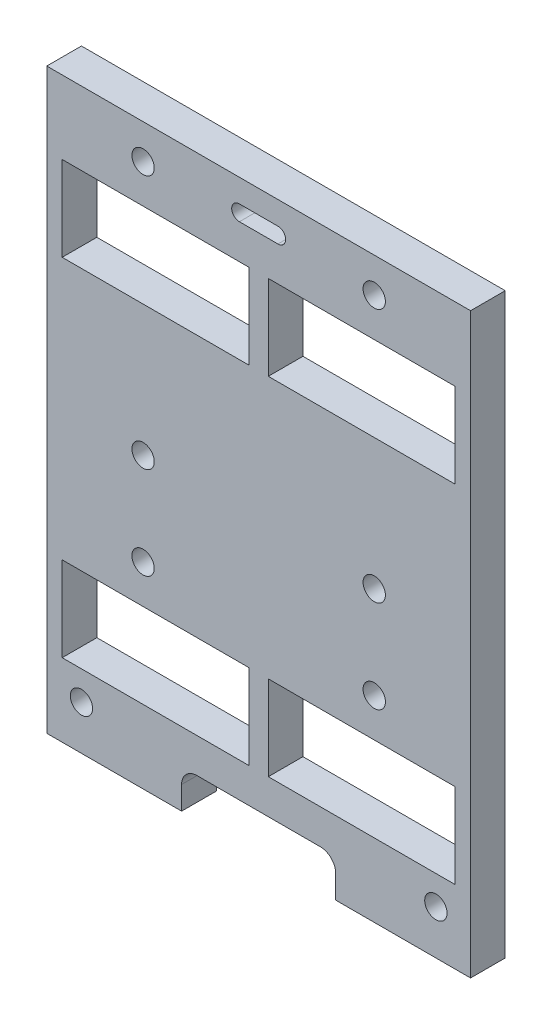
SolidWorks part; units mm, degrees
ref_plane "Front Plane" through (0, 0, 0) normal (0, 0, 1) x (1, 0, 0)
ref_plane "Top Plane" through (0, 0, 0) normal (0, 1, 0) x (1, 0, 0)
ref_plane "Right Plane" through (0, 0, 0) normal (1, 0, 0) x (0, 0, -1)
sketch "Sketch1" plane through (0, 0, 0) normal (0, 0, 1) x (1, 0, 0)
  line L0 (0, -37.5) -> (0, 37.5) construction
  line L1 (-27.5, -37.5) -> (27.5, -37.5)
  line L2 (-27.5, -37.5) -> (-27.5, 37.5)
  line L3 (-27.5, 37.5) -> (27.5, 37.5)
  line L4 (27.5, -37.5) -> (27.5, 37.5)
  line L5 (-27.5, -37.5) -> (27.5, 37.5) construction
  line L6 (-27.5, 37.5) -> (27.5, -37.5) construction
  line L7 (-27.5, 0) -> (27.5, 0) construction
  line L8 (-27.5, 22.5) -> (27.5, 22.5) construction
  line L9 (25.5, 17) -> (1.25, 28) construction
  line L10 (-25.5, 28) -> (-1.25, 28)
  line L11 (-25.5, 28) -> (-25.5, 17)
  line L12 (-25.5, 17) -> (-1.25, 17)
  line L13 (-1.25, 28) -> (-1.25, 17)
  line L14 (-25.5, 28) -> (-1.25, 17) construction
  line L15 (-25.5, 17) -> (-1.25, 28) construction
  line L16 (25.5, 28) -> (1.25, 17) construction
  line L17 (1.25, 28) -> (1.25, 17)
  line L18 (25.5, 17) -> (1.25, 17)
  line L19 (25.5, 28) -> (25.5, 17)
  line L20 (25.5, 28) -> (1.25, 28)
  line L21 (25.5, -28) -> (1.25, -17) construction
  line L22 (-25.5, -17) -> (-1.25, -28) construction
  line L23 (-25.5, -28) -> (-1.25, -17) construction
  line L24 (25.5, -17) -> (1.25, -28) construction
  line L25 (25.5, -28) -> (1.25, -28)
  line L26 (25.5, -28) -> (25.5, -17)
  line L27 (25.5, -17) -> (1.25, -17)
  line L28 (1.25, -28) -> (1.25, -17)
  line L29 (-1.25, -28) -> (-1.25, -17)
  line L30 (-25.5, -17) -> (-1.25, -17)
  line L31 (-25.5, -28) -> (-25.5, -17)
  line L32 (-25.5, -28) -> (-1.25, -28)
  point P0 (0, 0)
  point P12 (-13.375, 22.5)
  point P21 (13.375, 22.5)
  point P30 (13.375, -22.5)
  point P31 (-13.375, -22.5)
  dimension "D1" = 55
  dimension "D2" = 75
  dimension "D3" = 22.5
  dimension "D4" = 24.25
  dimension "D5" = 11
  dimension "D6" = 1.25
extrude "Boss-Extrude1" add sketch "Sketch1" along normal blind 4.5
sketch "Sketch2" plane through (0, 0, 4.5) normal (0, 0, 1) x (1, 0, 0)
  line L0 (0, -37.5) -> (0, 37.5) construction
  line L1 (-27.5, -37.5) -> (27.5, -37.5) construction
  line L2 (27.5, 37.5) -> (-27.5, 37.5) construction
  line L3 (-27.5, 0) -> (27.5, 0) construction
  line L4 (-27.5, 37.5) -> (-27.5, -37.5) construction
  line L5 (27.5, -37.5) -> (27.5, 37.5) construction
  line L6 (-15, 0) -> (15, 0) construction
  circle A0 centre (-15, 33) radius 1.45
  circle A1 centre (15, 33) radius 1.45
  circle A2 centre (15, 0) radius 1.45
  circle A3 centre (-15, 0) radius 1.45
  dimension "D1" = 2.9
  dimension "D7" = 2.9
  dimension "D8" = 2.9
  dimension "D2" = 15
  dimension "D3" = 33
  dimension "D4" = 30
  dimension "D5" = 15
  dimension "D6" = 0
extrude "screwHoles" cut sketch "Sketch2" against normal through all
sketch "Sketch3" plane through (0, 0, 4.5) normal (0, 0, 1) x (1, 0, 0)
  line L0 (-27.5, 9) -> (26.0486, 9) construction
  line L1 (-27.5, 37.5) -> (-27.5, -37.5) construction
  line L3 (0, 37.5) -> (0, -37.5) construction
  line L4 (27.5, 37.5) -> (-27.5, 37.5) construction
  line L5 (-27.5, -37.5) -> (27.5, -37.5) construction
  line L6 (18.95, 6.8) -> (9.05, 11.2) construction
  line L7 (-18.95, 11.2) -> (-9.05, 11.2)
  line L8 (-18.95, 11.2) -> (-18.95, 6.8)
  line L9 (-18.95, 6.8) -> (-9.05, 6.8)
  line L10 (-9.05, 11.2) -> (-9.05, 6.8)
  line L11 (-18.95, 11.2) -> (-9.05, 6.8) construction
  line L12 (-18.95, 6.8) -> (-9.05, 11.2) construction
  line L13 (18.95, 11.2) -> (9.05, 6.8) construction
  line L14 (9.05, 11.2) -> (9.05, 6.8)
  line L15 (18.95, 6.8) -> (9.05, 6.8)
  line L16 (18.95, 11.2) -> (18.95, 6.8)
  line L17 (18.95, 11.2) -> (9.05, 11.2)
  line L18 (-27.5, 37.5) -> (-27.5, -37.5) construction
  point P2 (-27.5, 0)
  point P12 (-14, 9)
  point P21 (14, 9)
  dimension "D1" = 9.9
  dimension "D3" = 14
  dimension "D4" = 9
extrude "BeltClamp" [suppressed] cut sketch "Sketch3" against normal through all
sketch "Sketch4" plane through (0, 0, 4.5) normal (0, 0, 1) x (1, 0, 0)
  line L0 (-27.5, 0) -> (27.5, 0) construction
  line L1 (-27.5, 37.5) -> (-27.5, -37.5) construction
  line L2 (27.5, -37.5) -> (27.5, 37.5) construction
  line L4 (-4.85, 2.175) -> (4.85, 2.175)
  line L5 (-4.85, 2.175) -> (-4.85, -2.175)
  line L6 (-4.85, -2.175) -> (4.85, -2.175)
  line L7 (4.85, 2.175) -> (4.85, -2.175)
  line L8 (-4.85, 2.175) -> (4.85, -2.175) construction
  line L9 (-4.85, -2.175) -> (4.85, 2.175) construction
  circle A0 centre (-15, 0) radius 1.45 construction
  point P6 (0, 0)
  dimension "D2" = 4.35
  dimension "D3" = 0
extrude "mountingPlateTab" [suppressed] cut sketch "Sketch4" against normal through all
sketch "Sketch5" plane through (0, 0, 4.5) normal (0, 0, 1) x (1, 0, 0)
  line L0 (-27.5, -9.75) -> (27.5, -9.75) construction
  line L1 (-27.5, 37.5) -> (-27.5, -37.5) construction
  line L2 (27.5, -37.5) -> (27.5, 37.5) construction
  line L4 (0, -37.5) -> (0, 37.5) construction
  line L5 (-27.5, -37.5) -> (27.5, -37.5) construction
  line L6 (27.5, 37.5) -> (-27.5, 37.5) construction
  line L7 (-20.825, -14.6) -> (-25.175, -4.9) construction
  line L8 (20.825, -4.9) -> (25.175, -4.9)
  line L9 (20.825, -4.9) -> (20.825, -14.6)
  line L10 (20.825, -14.6) -> (25.175, -14.6)
  line L11 (25.175, -4.9) -> (25.175, -14.6)
  line L12 (20.825, -4.9) -> (25.175, -14.6) construction
  line L13 (20.825, -14.6) -> (25.175, -4.9) construction
  line L14 (-20.825, -4.9) -> (-25.175, -14.6) construction
  line L15 (-25.175, -4.9) -> (-25.175, -14.6)
  line L16 (-20.825, -14.6) -> (-25.175, -14.6)
  line L17 (-20.825, -4.9) -> (-20.825, -14.6)
  line L18 (-20.825, -4.9) -> (-25.175, -4.9)
  line L19 (23, -9.75) -> (23, -37.5) construction
  line L20 (-23, -9.75) -> (-23, -37.5) construction
  circle A0 centre (23, -31.75) radius 1.45
  circle A1 centre (-23, -31.75) radius 1.45
  point P15 (23, -9.75)
  point P24 (-23, -9.75)
  dimension "D5" = 2.9
  dimension "D2" = 9.7
  dimension "D3" = 4.35
  dimension "D4" = 23
  dimension "D6" = 22
  dimension "D1" = 9.75
extrude "BraceTabs" cut sketch "Sketch5" against normal through all
sketch "Sketch6" [suppressed] plane through (0, 0, 4.5) normal (0, 0, 1) x (1, 0, 0)
  line L0 (-25.175, -9.75) -> (25.175, -9.75) construction
  line L1 (-25.175, -4.9) -> (-25.175, -14.6) construction
  line L2 (25.175, -14.6) -> (25.175, -4.9) construction
  line L3 (0, -2.175) -> (0, -37.5) construction
  line L4 (-4.85, -2.175) -> (4.85, -2.175) construction
  line L5 (-27.5, -37.5) -> (27.5, -37.5) construction
  line L6 (23, -14.6) -> (23, -4.9) construction
  line L7 (20.825, -14.6) -> (25.175, -14.6) construction
  line L8 (25.175, -4.9) -> (20.825, -4.9) construction
  line L9 (20.825, -4.9) -> (20.825, -14.6) construction
  line L10 (19.825, -15.6) -> (26.175, -15.6)
  line L11 (19.825, -15.6) -> (19.825, -3.9)
  line L12 (19.825, -3.9) -> (26.175, -3.9)
  line L13 (26.175, -15.6) -> (26.175, -3.9)
  line L14 (19.825, -15.6) -> (26.175, -3.9) construction
  line L15 (19.825, -3.9) -> (26.175, -15.6) construction
  line L16 (-19.825, -3.9) -> (-26.175, -15.6) construction
  line L17 (-19.825, -15.6) -> (-26.175, -3.9) construction
  line L18 (-23, -14.6) -> (-23, -4.9) construction
  line L19 (-26.175, -15.6) -> (-26.175, -3.9)
  line L20 (-19.825, -3.9) -> (-26.175, -3.9)
  line L21 (-19.825, -15.6) -> (-19.825, -3.9)
  line L22 (-19.825, -15.6) -> (-26.175, -15.6)
  circle A0 centre (23, -9.75) radius 1.45
  circle A1 centre (-23, -9.75) radius 1.45
  point P18 (23, -9.75)
  dimension "D3" = 2.9
  dimension "D1" = 1
  dimension "D2" = 1
extrude "FrontToRear1" [suppressed] add sketch "Sketch6" against normal up to surface (4.5 mm away) up to face at (-24.45, -31.75, 0)
sketch "Sketch7" [suppressed] plane through (0, 0, 4.5) normal (0, 0, 1) x (1, 0, 0)
  line L0 (4.85, 2.175) -> (-4.85, 2.175) construction
  line L1 (-20, -3.175) -> (20, -3.175)
  line L2 (-20, -3.175) -> (-20, 3.175)
  line L3 (-20, 3.175) -> (20, 3.175)
  line L4 (20, -3.175) -> (20, 3.175)
  line L5 (-20, -3.175) -> (20, 3.175) construction
  line L6 (-20, 3.175) -> (20, -3.175) construction
  circle A0 centre (15, 0) radius 1.45 construction
  point P0 (0, 0)
  dimension "D1" = 1
  dimension "D2" = 5
extrude "FrontToRear2" [suppressed] add sketch "Sketch7" against normal through all
sketch "Sketch8" plane through (0, 0, 4.5) normal (0, 0, 1) x (1, 0, 0)
  line L0 (-27.5, -12) -> (27.5, -12) construction
  line L1 (-27.5, 37.5) -> (-27.5, -37.5) construction
  line L2 (27.5, -37.5) -> (27.5, 37.5) construction
  line L3 (0, -37.5) -> (0, 0) construction
  line L4 (-27.5, -37.5) -> (27.5, -37.5) construction
  circle A0 centre (-15, -12) radius 1.45
  circle A1 centre (15, -12) radius 1.45
  dimension "D2" = 2.9
  dimension "D1" = 12
  dimension "D3" = 15
extrude "ExpansionScrewholes" cut sketch "Sketch8" against normal through all
sketch "Sketch12" plane through (0, 0, 4.5) normal (0, 0, 1) x (1, 0, 0)
  line L0 (0, 37.5) -> (0, 0) construction
  line L1 (27.5, 37.5) -> (-27.5, 37.5) construction
  line L2 (-2.5, 33.5) -> (2.5, 33.5) construction
  line L3 (-2.5, 34.5) -> (2.5, 34.5)
  line L4 (-2.5, 32.5) -> (2.5, 32.5)
  arc A0 (-2.5, 34.5) -> (-2.5, 32.5) centre (-2.5, 33.5) ccw
  arc A1 (2.5, 32.5) -> (2.5, 34.5) centre (2.5, 33.5) ccw
  point P7 (0, 33.5)
  dimension "D1" = 3
  dimension "D2" = 2
  dimension "D3" = 5
extrude "CableTieSlot" cut sketch "Sketch12" against normal through all
sketch "Sketch11" plane through (0, 0, 4.5) normal (0, 0, 1) x (1, 0, 0)
  line L0 (13.5615, -8.6) -> (27.5, -8.6) construction
  line L1 (27.5, -37.5) -> (27.5, 37.5) construction
  line L2 (0, 37.5) -> (0, -37.5) construction
  line L3 (36.5, -14.6) -> (18.5, -14.6)
  line L4 (36.5, -14.6) -> (36.5, -2.6)
  line L5 (36.5, -2.6) -> (18.5, -2.6)
  line L6 (18.5, -14.6) -> (18.5, -2.6)
  line L7 (36.5, -14.6) -> (18.5, -2.6) construction
  line L8 (36.5, -2.6) -> (18.5, -14.6) construction
  line L11 (-36.5, -2.6) -> (-18.5, -14.6) construction
  line L12 (-36.5, -14.6) -> (-18.5, -2.6) construction
  line L13 (-18.5, -14.6) -> (-18.5, -2.6)
  line L14 (-36.5, -2.6) -> (-18.5, -2.6)
  line L15 (-36.5, -14.6) -> (-36.5, -2.6)
  line L16 (-36.5, -14.6) -> (-18.5, -14.6)
  line L17 (36.5, -2.6) -> (18.5, -14.6) construction
  line L18 (20.825, -14.6) -> (25.175, -14.6) construction
  line L19 (27.5, 37.5) -> (-27.5, 37.5) construction
  line L20 (-27.5, -37.5) -> (27.5, -37.5) construction
  dimension "D1" = 9
  dimension "D2" = 12
  dimension "D3" = 0
extrude "Cut-Extrude2" [suppressed] cut sketch "Sketch11" against normal through all
sketch "Sketch10" [suppressed] plane through (0, 0, 4.5) normal (0, 0, 1) x (1, 0, 0)
  line L0 (4.7446, 1) -> (27.5, 1) construction
  line L1 (-4.85, 0) -> (4.85, 0) construction
  line L2 (27.5, -37.5) -> (27.5, 37.5) construction
  line L3 (0, 2.175) -> (0, -2.175) construction
  line L4 (36.5, 4) -> (18.5, 4)
  line L5 (36.5, 4) -> (36.5, -2)
  line L6 (36.5, -2) -> (18.5, -2)
  line L7 (18.5, 4) -> (18.5, -2)
  line L8 (36.5, 4) -> (18.5, -2) construction
  line L9 (36.5, -2) -> (18.5, 4) construction
  line L10 (4.85, 2.175) -> (-4.85, 2.175) construction
  line L11 (-4.85, -2.175) -> (4.85, -2.175) construction
  line L12 (-36.5, -2) -> (-18.5, 4) construction
  line L13 (-36.5, 4) -> (-18.5, -2) construction
  line L14 (-4.7446, 1) -> (-27.5, 1) construction
  line L15 (-18.5, 4) -> (-18.5, -2)
  line L16 (-36.5, -2) -> (-18.5, -2)
  line L17 (-36.5, 4) -> (-36.5, -2)
  line L18 (-36.5, 4) -> (-18.5, 4)
  line L19 (36.5, -2) -> (18.5, 4) construction
  line L20 (-4.85, 2.175) -> (-4.85, -2.175) construction
  line L21 (4.85, -2.175) -> (4.85, 2.175) construction
  dimension "D1" = 6
  dimension "D2" = 9
  dimension "D3" = 1
extrude "CableTieSlots" [suppressed] cut sketch "Sketch10" against normal through all
sketch "Sketch9" plane through (0, 0, 4.5) normal (0, 0, 1) x (1, 0, 0)
  line L0 (-27.5, -37.5) -> (27.5, -37.5) construction
  line L5 (-10, -42.5) -> (10, -42.5)
  line L6 (-10, -42.5) -> (-10, -34.5)
  line L7 (-8, -32.5) -> (8, -32.5)
  line L8 (10, -42.5) -> (10, -34.5)
  line L9 (-10, -42.5) -> (10, -32.5) construction
  line L10 (-10, -32.5) -> (10, -42.5) construction
  arc A0 (8, -32.5) -> (10, -34.5) centre (8, -34.5) cw
  arc A1 (-10, -34.5) -> (-8, -32.5) centre (-8, -34.5) cw
  point P9 (0, -37.5)
  line M42 (-27.5, -37.5) -> (27.5, -37.5)
  dimension "D3" = 2
  dimension "D1" = 20
  dimension "D2" = 5
extrude "RearFanSlot" cut sketch "Sketch9" against normal through all contours A1 L6 L8 A0 L7 M42 | L5 L8 L6 M42
sketch "Sketch13" [suppressed] plane through (0, 0, 4.5) normal (0, 0, 1) x (1, 0, 0)
  line L1 (-7, -2.85) -> (7, -2.85)
  line L2 (-7, -2.85) -> (-7, -11.85)
  line L3 (-7, -11.85) -> (7, -11.85)
  line L4 (7, -2.85) -> (7, -11.85)
  line L5 (-7, -2.85) -> (7, -11.85) construction
  line L6 (-7, -11.85) -> (7, -2.85) construction
  line L9 (0, 37.5) -> (0, -7.35) construction
  line L10 (-18.5, -2.85) -> (-27.5, -2.85) construction
  line L11 (27.5, 37.5) -> (-27.5, 37.5) construction
  line L13 (-27.5, -14.85) -> (-18.5, -14.85) construction
  point P0 (0, -7.35)
  dimension "D1" = 3
  dimension "D2" = 0
  dimension "D3" = 7
extrude "Cut-Extrude3" [suppressed] cut sketch "Sketch13" against normal through all
sketch "Sketch14" plane through (0, 0, 4.5) normal (0, 0, 1) x (1, 0, 0)
  line L0 (25.175, -4.9) -> (20.825, -4.9) construction
  line L1 (25.175, -4.9) -> (20.825, -4.9)
  line L2 (25.175, -4.9) -> (25.175, -14.6)
  line L3 (25.175, -14.6) -> (20.825, -14.6)
  line L4 (20.825, -4.9) -> (20.825, -14.6)
  line L5 (25.175, -14.6) -> (25.175, -4.9) construction
  line L6 (0, 0) -> (0, -6.835) construction
  line L7 (-20.825, -4.9) -> (-20.825, -14.6)
  line L8 (-25.175, -14.6) -> (-20.825, -14.6)
  line L9 (-25.175, -4.9) -> (-25.175, -14.6)
  line L10 (-25.175, -4.9) -> (-20.825, -4.9)
extrude "Boss-Extrude2" add sketch "Sketch14" against normal through all
equation "\"X-ROD-SPACING\"=45"
equation "\"Y-ROD-SPACING\"=75"
equation "\"Z-ROD-SPACING\"=17.5"
equation "\"Y-BED-OFFSET\"=2"
equation "\"Y-BED-ROD-INSET\"=3.5"
equation "\"Y-BED-SCREW-SPACING\"=209"
equation "\"Y-BED-SCREW-CUTOUT-SLOT-HEIGHT\"=2.5"
equation "\"T-SLOT-NUT-FILLET-RADIUS\"=0.5"
equation "\"T-SLOT-SCREW-SHAFT-RADIUS\"=1.55"
equation "\"T-SLOT-SCREW-SHAFT-CUTOUT-LENGTH\"=11"
equation "\"T-SLOT-NUT-DEPTH\"=3.5"
equation "\"T-SLOT-NUT-WIDTH\"=2.85"
equation "\"T-SLOT-NUT-END-DISTANCE\"=8"
equation "\"ACRYLIC-THICKNESS\"=10"
equation "\"ACRYLIC-THICKNESS2\"=4.5"
equation "\"ACRYLIC-TAB-CUTOUT-SIZE\"=\"ACRYLIC-THICKNESS\"+\"ACRYLIC-TAB-TOLERANCE\"*2"
equation "\"ACRYLIC-TAB-WIDTH\"=\"ACRYLIC-THICKNESS\""
equation "\"ACRYLIC-M3-HOLE\"=2.9"
equation "\"SMOOTHROD-CAP-SCREW-DISTANCE\"=20"
equation "\"FRAME-WIDTH-INNER\"=370"
equation "\"NEMA17-HOLE-SPACING\"=31"
equation "\"NEMA17-CENTRAL-CUTOUT\"=22.5"
equation "\"Z-BRACKET-REACH\"=57"
equation "\"Z-ROD-INSET\"=13.5"
equation "\"TOP-BRACKET-SPACING\"=40"
equation "\"SMOOTHROD-X-LENGTH\"=350"
equation "\"SMOOTHROD-Y-LENGTH\"=350"
equation "\"SMOOTHROD-Z-LENGTH\"=350"
equation "\"SMOOTHROD-TIGHTENING-HEADROOM\"=.25"
equation "\"LEADSCREW-Z-LENGTH\"=300"
equation "\"SCREW-LENGTH-FRAME\"=\"ACRYLIC-THICKNESS\" + 10"
equation "\"SCREW-LENGTH-MOTOR\"=\"ACRYLIC-THICKNESS\" + 5"
equation "\"SCREW-HEAD-RADIUS\"=6"
equation "\"PRINTED-X-SMOOTHROD-DIAMETER\"=8.8"
equation "\"PRINTED-X-SMOOTHROD-CUTOUT\"=10"
equation "\"PRINTED-X-BASE-HEIGHT\"=10"
equation "\"PRINTED-LM8UU-CUTOUT-SIZE\"=15.5"
equation "\"PRINTED-LM8UU-CUTOUT-LENGTH\"=24.5"
equation "\"PRINTED-X-IDLER-HEIGHT\"=16"
equation "\"PSU-MOUNTING-WIDTH\"=50"
equation "\"PSU-MOUNTING-HEIGHT\"=150"
equation "\"Y-BELT-TO-ROD-DISTANCE\"=20"
equation "\"SPOOL-HOLDER-ROD-SPACING\"=150"
equation "\"D3@Sketch1\"=\"X-ROD-SPACING\"/2"
equation "\"D4@Sketch1\"=\"ACRYLIC-X-CARRIAGE-LM8UU-CUTOUT-WIDTH\""
equation "\"D1@Boss-Extrude1\"=\"ACRYLIC-THICKNESS2\""
equation "\"D1@Sketch2\"=\"ACRYLIC-M3-HOLE\""
equation "\"D1@Sketch3\"=\"ACRYLIC-TAB-CUTOUT-SIZE\""
equation "\"D2@Sketch3\"=\"ACRYLIC-THICKNESS2\"+\"ACRYLIC-TAB-TOLERANCE\"*2"
equation "\"ACRYLIC-X-CARRIAGE-WIDTH\"=55"
equation "\"ACRYLIC-X-CARRIAGE-HEIGHT\"=75"
equation "\"D1@Sketch1\"=\"ACRYLIC-X-CARRIAGE-WIDTH\""
equation "\"D2@Sketch1\"=\"ACRYLIC-X-CARRIAGE-HEIGHT\""
equation "\"ACRYLIC-X-CARRIAGE-CENTER-TAB-SPACING\"=14"
equation "\"D3@Sketch3\"=\"ACRYLIC-X-CARRIAGE-CENTER-TAB-SPACING\""
equation "\"SCREW-LENGTH-EXTRUDER\"=28"
equation "\"ACRYLIC-X-CARRIAGE-SCREW-SPACING-X\"=15"
equation "\"ACRYLIC-X-CARRIAGE-SCREW-SPACING-Y\"=33"
equation "\"D2@Sketch2\"=\"ACRYLIC-X-CARRIAGE-SCREW-SPACING-X\""
equation "\"D3@Sketch2\"=\"ACRYLIC-X-CARRIAGE-SCREW-SPACING-Y\""
equation "\"D1@Sketch4\"=\"ACRYLIC-TAB-WIDTH\"-\"KERF\"*4"
equation "\"D2@Sketch4\"=\"ACRYLIC-THICKNESS2\"-\"KERF\"*2"
equation "\"D2@Sketch5\"=\"ACRYLIC-TAB-WIDTH\"-\"KERF\"*4"
equation "\"D3@Sketch5\"=\"ACRYLIC-THICKNESS2\"-\"KERF\"*2"
equation "\"ACRYLIC-X-CARRIAGE-EXTRUDER-SHELF-DEPTH\"=\"ACRYLIC-X-CARRIAGE-EXTRUDER-OFFSET\" + 28"
equation "\"ACRYLIC-X-CARRIAGE-EXTRUDER-BRACE-SPACING\"=23"
equation "\"D4@Sketch5\"=\"ACRYLIC-X-CARRIAGE-EXTRUDER-BRACE-SPACING\""
equation "\"D4@Sketch2\"=\"ACRYLIC-X-CARRIAGE-SCREW-SPACING-X\"*2"
equation "\"D5@Sketch2\"=\"ACRYLIC-X-CARRIAGE-SCREW-SPACING-X\""
equation "\"D7@Sketch2\"=\"ACRYLIC-M3-HOLE\""
equation "\"D8@Sketch2\"=\"ACRYLIC-M3-HOLE\""
equation "\"ACRYLIC-X-CARRIAGE-LM8UU-CUTOUT-WIDTH\"=24.25"
equation "\"ACRYLIC-TAB-TOLERANCE\"=-.05"
equation "\"ACRYLIC-X-CARRIAGE-EXTRUDER-OFFSET\"=26"
equation "\"ACRYLIC-X-CARRIAGE-EXTRUDER-ANGLE\"=90"
equation "\"ACRYLIC-X-CARRIAGE-EXTRUDER-BRACE-TAB-OFFSET\"=20"
equation "\"ACRYLIC-X-CARRIAGE-EXTRUDER-BRACE-HEIGHT\"=35"
equation "\"ACRYLIC-X-CARRIAGE-EXTRUDER-BRACE-SCREW-SPACING\"=22"
equation "\"D5@Sketch5\"=\"ACRYLIC-M3-HOLE\""
equation "\"D3@Sketch6\"=\"ACRYLIC-M3-HOLE\""
equation "\"ACRYLIC-X-CARRIAGE-LM8UU-CUTOUT-HEIGHT\"=11.0"
equation "\"ACRYLIC-X-CARRIAGE-DUAL-WIDTH-MULTIPLIER\"=1.65"
equation "\"ACRYLIC-X-CARRIAGE-DUAL-HOTEND-SPACING\"=42"
equation "\"ACRYLIC-X-CARRIAGE-DUAL-WIDTH\"=75"
equation "\"ACRYLIC-X-CARRIAGE-DUAL-HOTEND-SEPARATION\"=36"
equation "\"ACRYLIC-X-CARRIAGE-DUAL-MOUNT-PLATE-DEPTH\"=75"
equation "\"ACRYLIC-X-CARRIAGE-DUAL-MOUNT-BRACE-WIDTH\"=33"
equation "\"ACRYLIC-X-CARRIAGE-DUAL-MOUNT-SCREW-WIDTH\"=40"
equation "\"D5@Sketch1\"=\"ACRYLIC-X-CARRIAGE-LM8UU-CUTOUT-HEIGHT\""
equation "\"D2@Sketch8\"=\"ACRYLIC-M3-HOLE\""
equation "\"D1@Sketch5\"=\"ACRYLIC-THICKNESS2\"/2 + 7.5"
equation "\"KERF\"=0.075"
equation "\"PRINTED-M3-HOLE\"=3.5"
equation "\"PRINTED-M3-NUT-AF\"=6.25"
equation "\"ACRYLIC-X-CARRIAGE-DUAL-FAN-OFFSET\"=52"
equation "\"ACRYLIC-X-CARRIAGE-DUAL-FAN-HEIGHT\"=20"
equation "\"BLOWER-FAN-WIDTH\"=15"
